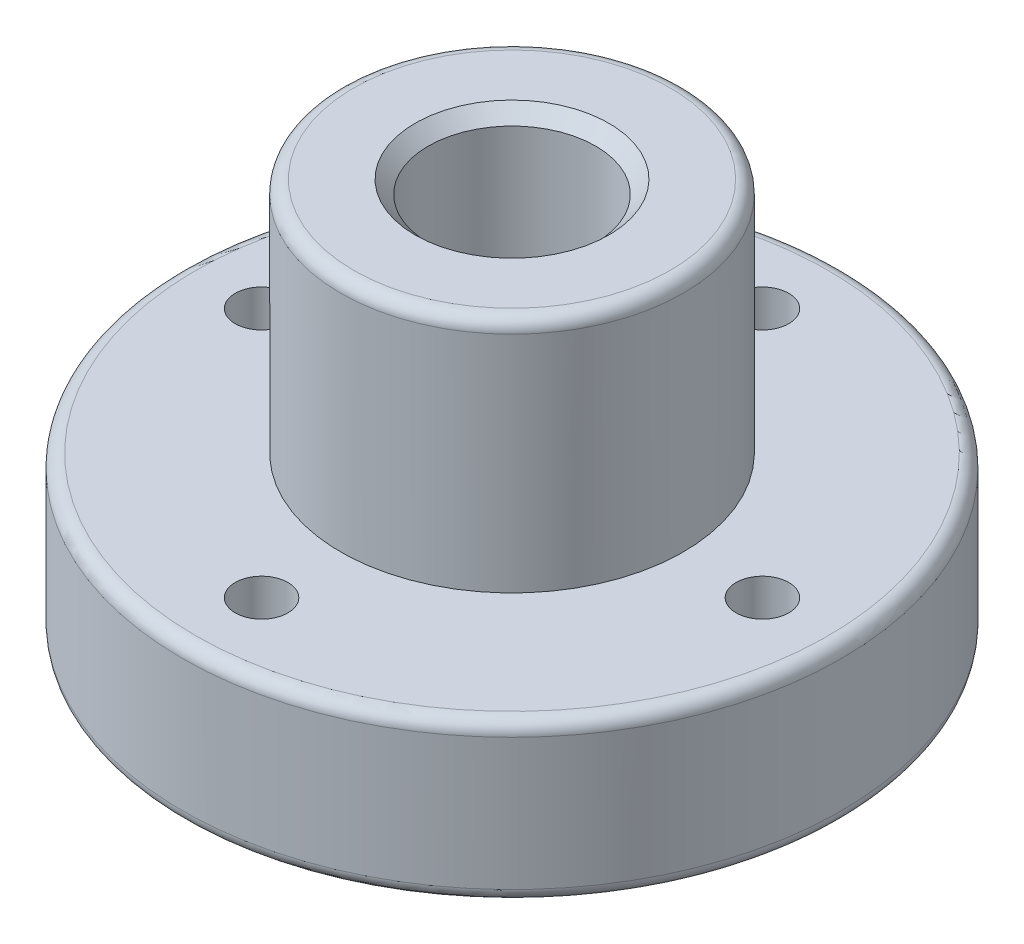
SolidWorks part; units mm, degrees
ref_plane "Plan de face" through (0, 0, 0) normal (0, 0, 1) x (1, 0, 0)
ref_plane "Plan de dessus" through (0, 0, 0) normal (0, 1, 0) x (1, 0, 0)
ref_plane "Plan de droite" through (0, 0, 0) normal (1, 0, 0) x (0, 0, -1)
sketch "Esquisse1" plane through (0, 0, 0) normal (0, 0, 1) x (1, 0, 0)
  line L0 (6.5, 15) -> (6.5, 6)
  line L1 (6.5, 6) -> (12.5, 6)
  line L2 (12.5, 6) -> (12.5, 0)
  line L9 (6.5, 15) -> (3.175, 15)
  line L10 (3.175, 15) -> (3.175, 0)
  line L11 (12.5, 0) -> (3.175, 0)
  line L12 (0, 0) -> (0, 15) construction
  dimension "D1" = 12.5
  dimension "D2" = 6
  dimension "D3" = 15
  dimension "D4" = 3.175
  dimension "D5" = 6
  dimension "D6" = 9.325
revolve "Révolution2" add sketch "Esquisse1" angle 360 about L12
sketch "Esquisse3" plane through (0, 6, 0) normal (0, 1, 0) x (1, 0, 0)
  line L0 (0, 0) -> (9.5, 0) construction
  circle A0 centre (9.5, 0) radius 1
  circle A2 centre (0, 0) radius 12.5 construction
  circle A3 centre (0, 0) radius 6.5 construction
  circle A8 centre (0, -9.5) radius 1
  circle A9 centre (-9.5, 0) radius 1
  circle A10 centre (0, 9.5) radius 1
  point P7 (6.5, 0)
  point P8 (12.5, 0)
  point P19 (0, 0)
  point P23 (0, -4.027)
  dimension "D1" = 2
  dimension "D3" = 3
  dimension "D2" = 3
  dimension "D4" = 4
extrude "Enlèv. mat.-Extru.1" cut sketch "Esquisse3" against normal through all
fillet "Congé1" radius 0.5 3 edges at (0, 15, -6.5) (0, 0, -12.5) (0, 6, -12.5)
chamfer "Chanfrein1" distance 0.5 angle 45 2 edges at (0, 0, -3.175) (0, 15, -3.175)
sketch "Esquisse8" [suppressed] plane through (0, -5.2608, 0) normal (0, 1, 0) x (1, 0, 0)
  circle A0 centre (8, 0) radius 0.8
  circle A4 centre (0, -8) radius 0.8
  circle A5 centre (-8, 0) radius 0.8
  circle A6 centre (0, 8) radius 0.8
  point P12 (0, 0)
  dimension "D1" = 1.6
  dimension "D3" = 4
  dimension "D2" = 8
extrude "Enlèv. mat.-Extru.2" [suppressed] cut sketch "Esquisse8" against normal through all
